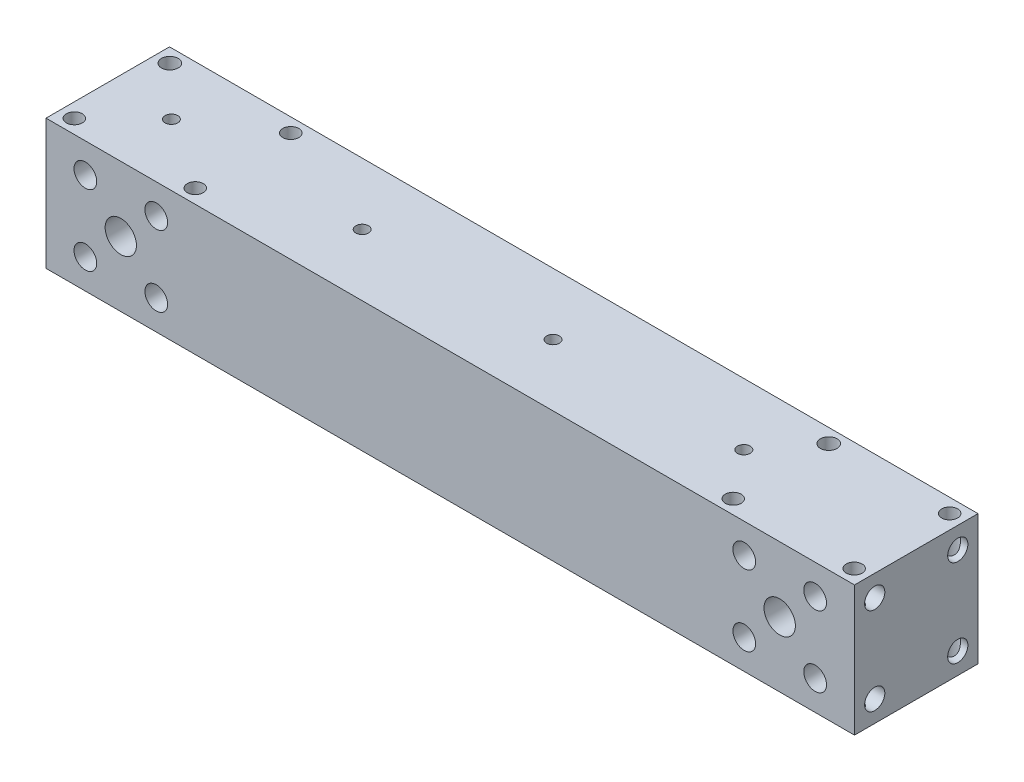
SolidWorks part; units mm, degrees
ref_plane "Front Plane" through (0, 0, 0) normal (0, 0, 1) x (1, 0, 0)
ref_plane "Top Plane" through (0, 0, 0) normal (0, 1, 0) x (1, 0, 0)
ref_plane "Right Plane" through (0, 0, 0) normal (1, 0, 0) x (0, 0, -1)
sketch "Sketch3" plane through (0, 0, 0) normal (0, 1, 0) x (1, 0, 0)
  line L0 (-122.5, -4.4) -> (-84.5, -4.4) construction
  line L1 (84.5, -4.4) -> (122.5, -4.4) construction
  point P3 (-103.5, -4.4)
  point P6 (103.5, -4.4)
  line B0 (-127, 0) -> (127, 0)
  line B1 (-127, 0) -> (-127, -38.8)
  line B2 (-127, -38.8) -> (127, -38.8)
  line B3 (127, 0) -> (127, -38.8)
  circle B4 centre (122.5, -4.4) radius 2.5
  circle B5 centre (122.5, -34.4) radius 2.5
  circle B6 centre (84.5, -34.4) radius 2.5
  circle B7 centre (84.5, -4.4) radius 2.627
  circle B8 centre (-84.5, -4.4) radius 2.5
  circle B9 centre (-84.5, -34.4) radius 2.5
  circle B10 centre (-122.5, -34.4) radius 2.5
  circle B11 centre (-122.5, -4.4) radius 2.627
sketch_block_instance "Block-LateralDirSliderMounting-1"
sketch_block "Block1"
sketch "Sketch4" plane through (0, 0, 0) normal (0, 0, 1) x (1, 0, 0)
  line L0 (-127, 40.8781) -> (-127, 0)
  line L1 (-127, 0) -> (127, 0)
  line L2 (127, 0) -> (127, 40.8781)
  line L3 (-127, 40.8781) -> (127, 40.8781)
  circle B0 centre (-103.5, 20.4391) radius 20.4391
  circle B1 centre (-92.3645, 31.5746) radius 3.5719
  circle B2 centre (-92.3645, 9.3035) radius 3.5719
  circle B3 centre (-114.6355, 9.3035) radius 3.5719
  circle B4 centre (-114.6355, 31.5746) radius 3.5719
  circle B5 centre (-103.5, 20.4391) radius 4.9213
  circle B6 centre (103.5, 20.4391) radius 20.4391
  circle B7 centre (114.6355, 31.5746) radius 3.5719
  circle B8 centre (114.6355, 9.3035) radius 3.5719
  circle B9 centre (92.3645, 9.3035) radius 3.5719
  circle B10 centre (92.3645, 31.5746) radius 3.5719
  circle B11 centre (103.5, 20.4391) radius 4.9213
sketch_block_instance "Block-RailTravellerMounting-1"
sketch_block "Block-RailTravellerMounting"
sketch_block_instance "Block-RailTravellerMounting-2"
extrude "Boss-Extrude1" add sketch "Sketch3" along normal up to vertex (40.8781 mm away) contours B3 B0 B1 B2 B11 B10 B9 B8 B7 B6 B5 B4 | B11 | B8 | B10 | B9 | B7 | B4 | B5 | B6 region at (0.008, 0, 19.4063) up to point (-127, 40.8781, 0)
extrude "Cut-Extrude2" cut sketch "Sketch4" along normal through all contours B7 | B10 | B8 | B11 | B9 | B1 | B4 | B5 | B2 | B3 region at (-92.3645, 31.5746, 0) region at (-92.3645, 9.3035, 0) region at (-114.6355, 9.3035, 0) region at (-114.6355, 31.5746, 0) region at (-103.5, 20.4391, 0) region at (114.6355, 31.5746, 0) region at (114.6355, 9.3035, 0) region at (92.3645, 9.3035, 0) region at (92.3645, 31.5746, 0) region at (103.5, 20.4391, 0)
extrude "Cut-Extrude3" cut sketch "Sketch3<3>" along normal through all contours B10 | B9 | B11 | B8 | B6 | B5 | B4 | B7 region at (122.5, 0, 4.4) region at (122.5, 0, 34.4) region at (84.5, 0, 34.4) region at (84.5, 0, 4.4) region at (-84.5, 0, 4.4) region at (-84.5, 0, 34.4) region at (-122.5, 0, 34.4) region at (-122.5, 0, 4.4)
sketch "Sketch3<3>" plane through (0, 0, 0) normal (0, 1, 0) x (1, 0, 0) same geometry as "Sketch3"
sketch "Sketch5" plane through (0, 40.8781, 0) normal (0, 1, 0) x (1, 0, 0)
  line L0 (-127, 0) -> (-127, -38.8) construction
  line L1 (-127, -38.8) -> (127, -38.8) construction
  point P0 (-127, -19.4)
  point P3 (-127, -19.4)
  line B0 (-127, -12.9) -> (-127, -25.9)
  line B1 (-127, -25.9) -> (127, -25.9)
  line B2 (127, -25.9) -> (127, -12.9)
  line B3 (127, -12.9) -> (-127, -12.9)
  circle B4 centre (72.832, -19.4) radius 2
  circle B5 centre (12.888, -19.4) radius 2
  circle B6 centre (-47.056, -19.4) radius 2
  circle B7 centre (-107, -19.4) radius 2
sketch_block_instance "Block-LateralDirSliderBaseMounting-1"
sketch_block "Block-LateralDirSliderBaseMounting"
extrude "Cut-Extrude4" cut sketch "Sketch5" against normal blind 12.7 contours B6 | B7 | B5 | B4 region at (72.832, 40.8781, 19.4) region at (12.888, 40.8781, 19.4) region at (-47.056, 40.8781, 19.4) region at (-107, 40.8781, 19.4)
sketch "Sketch6" plane through (-127, 0, 0) normal (-1, 0, 0) x (0, 0, 1)
  line B0 (0, 40.8781) -> (38.8, 0) construction
  line B1 (38.8, 40.8781) -> (0, 0) construction
  line B2 (0, 0) -> (38.8, 0)
  line B3 (38.8, 0) -> (38.8, 40.8781)
  line B4 (38.8, 40.8781) -> (0, 40.8781)
  line B5 (0, 40.8781) -> (0, 0)
  circle B6 centre (6.35, 34.188) radius 3.175
  arc B7 (19.5268, 112.9247) -> (19.3958, 122.448) centre (19.4, 117.6855) ccw
  circle B8 centre (32.45, 34.188) radius 3.175
  circle B9 centre (6.35, 6.6901) radius 3.175
  circle B10 centre (32.45, 6.6901) radius 3.175
  spline B11 degree 3 poles (19.3958, 122.448) (19.4014, 122.4312) (19.4011, 122.4127) (19.3897, 122.3792) (19.3794, 122.3643) (19.3441, 122.3249) (19.3154, 122.3048) (19.2261, 122.2491) (19.1629, 122.2199) (18.9719, 122.1352) (18.842, 122.0844) (18.4558, 121.9241) (18.2025, 121.809) (17.7142, 121.5413) (17.4782, 121.389) (17.0396, 121.0519) (16.8353, 120.8666) (16.4589, 120.4599) (16.2862, 120.2366) (15.9898, 119.7703) (15.8639, 119.5256) (15.6608, 119.011) (15.5831, 118.7389) (15.4835, 118.1939) (15.46, 117.9185) (15.4665, 117.3616) (15.497, 117.0819) (15.6097, 116.5404) (15.6918, 116.2756) (15.9103, 115.759) (16.0435, 115.5158) (16.352, 115.0562) (16.5294, 114.8381) (16.9177, 114.4388) (17.1276, 114.2581) (17.5761, 113.9314) (17.8163, 113.7852) (18.3124, 113.5302) (18.5701, 113.4214) (18.9619, 113.2718) (19.0936, 113.2247) (19.2879, 113.1455) (19.3526, 113.1181) (19.443, 113.0656) (19.4727, 113.0459) (19.5084, 113.0079) (19.5189, 112.9933) (19.5311, 112.9602) (19.5318, 112.9417) (19.5268, 112.9247) knots 0 0 0 0 0.003906 0.003906 0.007812 0.007812 0.015625 0.015625 0.03125 0.03125 0.0625 0.0625 0.125 0.125 0.1875 0.1875 0.25 0.25 0.3125 0.3125 0.375 0.375 0.4375 0.4375 0.5 0.5 0.5625 0.5625 0.625 0.625 0.6875 0.6875 0.75 0.75 0.8125 0.8125 0.875 0.875 0.9375 0.9375 0.96875 0.96875 0.984375 0.984375 0.992188 0.992188 0.996094 0.996094 1 1 1 1
sketch_block_instance "Block-LateralMotorPlate-1"
sketch_block "Block-LateralMotorPlate" parameters "D2"=6.35, "D1"=6.35
extrude "Cut-Extrude5" cut sketch "Sketch6" against normal blind 6.35 contours B6 | B8 | B10 | B9 region at (-127, 34.188, 6.35) region at (-127, 34.188, 32.45) region at (-127, 6.6901, 6.35) region at (-127, 6.6901, 32.45)
extrude "Cut-Extrude6" cut sketch "Sketch6<3>" along normal blind 6.35 from surface contours B6 | B8 | B10 | B9 region at (-127, 34.188, 6.35) region at (-127, 34.188, 32.45) region at (-127, 6.6901, 6.35) region at (-127, 6.6901, 32.45) starting at face at (127, 20.4391, 19.4)
sketch "Sketch6<3>" plane through (-127, 0, 0) normal (-1, 0, 0) x (0, 0, 1) same geometry as "Sketch6"
sketch "Sketch7" plane through (0, 0, 0) normal (0, 0, -1) x (-1, 0, 0)
  circle A0 centre (-103.5, 20.4391) radius 9.525
  circle A1 centre (103.5, 20.4391) radius 9.525
  dimension "D1" = 19.05
extrude "Cut-Extrude7" cut sketch "Sketch7" against normal blind 21.0185
